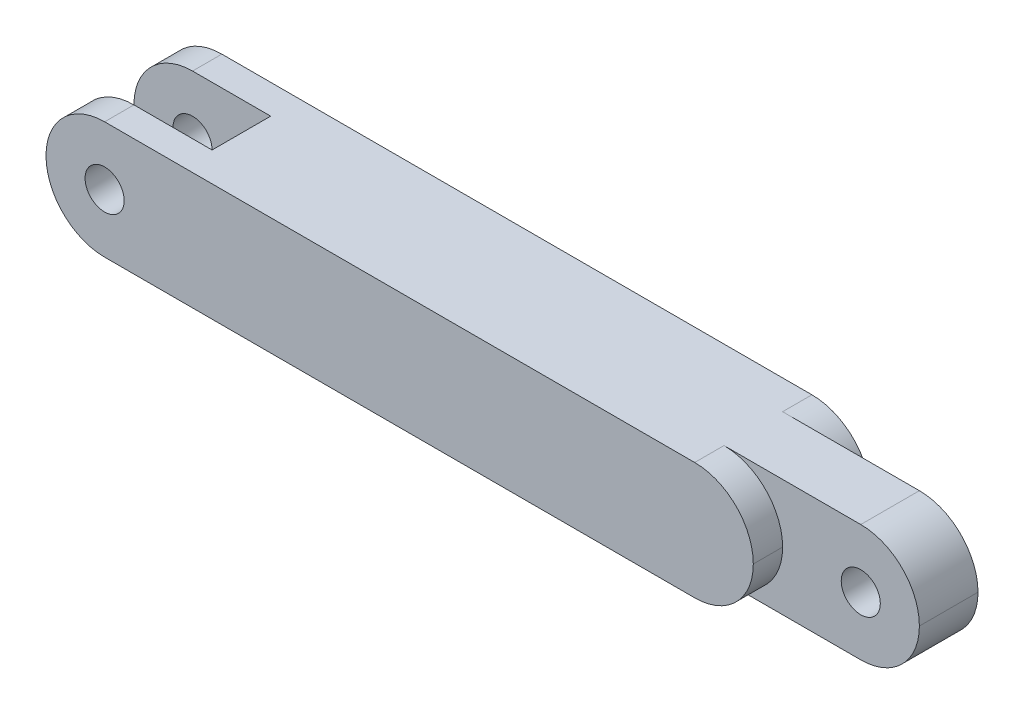
SolidWorks part; units mm, degrees
material "6061 Alloy"
ref_plane "Front Plane" through (0, 0, 0) normal (0, 0, 1) x (1, 0, 0)
ref_plane "Top Plane" through (0, 0, 0) normal (0, 1, 0) x (1, 0, 0)
ref_plane "Right Plane" through (0, 0, 0) normal (1, 0, 0) x (0, 0, -1)
sketch "Sketch1" plane through (0, 0, 0) normal (0, 0, 1) x (1, 0, 0)
  line L0 (0, 0) -> (0, 30)
  line L1 (0, 30) -> (216, 30)
  line L2 (216, 30) -> (216, 0)
  line L3 (216, 0) -> (0, 0)
  dimension "D1" = 30
  dimension "D2" = 216
extrude "Boss-Extrude1" add sketch "Sketch1" along normal mid plane 30
sketch "Sketch2" plane through (0, 30, 0) normal (0, 1, 0) x (1, 0, 0)
  line L0 (0, -7.5) -> (0, 7.5)
  line L1 (0, -15) -> (0, 15) construction
  line L2 (0, 7.5) -> (35, 7.5)
  line L3 (35, 7.5) -> (35, -7.5)
  line L4 (35, -7.5) -> (0, -7.5)
  line L5 (181, 15) -> (181, 7.5)
  line L6 (216, 15) -> (0, 15) construction
  line L7 (181, 7.5) -> (216, 7.5)
  line L8 (216, -15) -> (216, 15) construction
  line L9 (181, -15) -> (181, -7.5)
  line L10 (216, -15) -> (0, -15) construction
  line L11 (181, -7.5) -> (216, -7.5)
  line L12 (181, 15) -> (216, 15)
  line L13 (216, 15) -> (216, 7.5)
  line L14 (181, -15) -> (216, -15)
  line L15 (216, -15) -> (216, -7.5)
  point P6 (0, 0)
  dimension "D1" = 15
  dimension "D2" = 35
  dimension "D3" = 7.5
  dimension "D4" = 7.5
  dimension "D5" = 35
extrude "Cut-Extrude1" cut sketch "Sketch2" against normal up to next
fillet "Fillet1" radius 15 6 edges at (216, 0, 0) (216, 30, 0) (0, 0, 11.25) (0, 0, -11.25) (0, 30, -11.25) (0, 30, 11.25)
sketch "Sketch3" plane through (0, 0, 15) normal (0, 0, 1) x (1, 0, 0)
  circle A0 centre (15, 15) radius 5
  circle A1 centre (201, 15) radius 5
  dimension "D1" = 10
  dimension "D2" = 10
extrude "Cut-Extrude2" cut sketch "Sketch3" against normal through all both and the other way through all
fillet "Fillet3" radius 15 4 edges at (181, 0, -11.25) (181, 30, -11.25) (181, 0, 11.25) (181, 30, 11.25)
